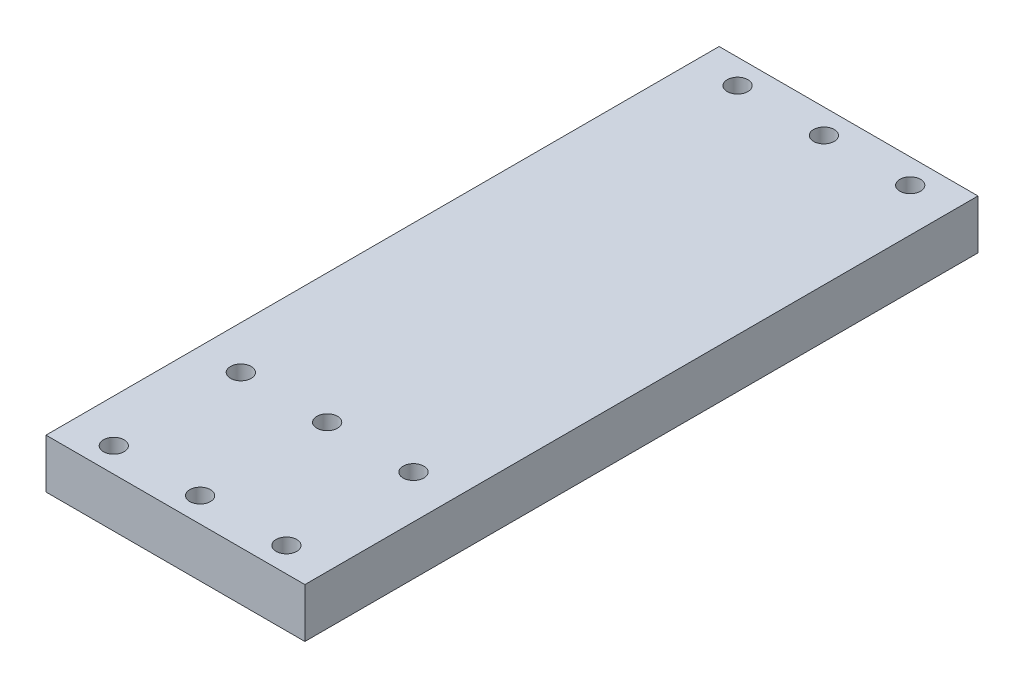
SolidWorks part; units mm, degrees
ref_plane "Front Plane" through (0, 0, 0) normal (0, 0, 1) x (1, 0, 0)
ref_plane "Top Plane" through (0, 0, 0) normal (0, 1, 0) x (1, 0, 0)
ref_plane "Right Plane" through (0, 0, 0) normal (1, 0, 0) x (0, 0, -1)
sketch "Sketch2" plane through (0, 0, 0) normal (0, 1, 0) x (1, 0, 0)
  line L1 (-25, -65) -> (25, -65)
  line L2 (-25, -65) -> (-25, 65)
  line L3 (-25, 65) -> (25, 65)
  line L4 (25, -65) -> (25, 65)
  line L5 (-25, -65) -> (25, 65) construction
  line L6 (-25, 65) -> (25, -65) construction
  point P0 (0, 0)
  dimension "D1" = 130
  dimension "D2" = 50
extrude "Boss-Extrude1" add sketch "Sketch2" along normal blind 9.525
sketch "Sketch3" plane through (0, 9.525, 0) normal (0, 1, 0) x (1, 0, 0)
  circle A0 centre (16.67, -60.2375) radius 2 construction
  circle A1 centre (0, -60.2375) radius 2 construction
  circle A2 centre (-16.67, -60.2375) radius 2 construction
  circle A3 centre (16.67, -35.7) radius 2 construction
  circle A4 centre (0, -35.7) radius 2 construction
  circle A5 centre (-16.67, -35.7) radius 2 construction
  circle A6 centre (16.67, 60.2375) radius 2 construction
  circle A7 centre (0, 60.2375) radius 2 construction
  circle A8 centre (-16.67, 60.2375) radius 2 construction
  circle A9 centre (16.67, -60.2375) radius 2
  circle A10 centre (0, -60.2375) radius 2
  circle A11 centre (-16.67, -60.2375) radius 2
  circle A12 centre (16.67, -35.7) radius 2
  circle A13 centre (0, -35.7) radius 2
  circle A14 centre (-16.67, -35.7) radius 2
  circle A15 centre (16.67, 60.2375) radius 2
  circle A16 centre (0, 60.2375) radius 2
  circle A17 centre (-16.67, 60.2375) radius 2
  point P29 (-16.67, 60.2375)
  point P32 (0, 60.2375)
  point P35 (16.67, 60.2375)
  point P38 (16.67, -35.7)
  point P41 (0, -35.7)
  point P44 (-16.67, -35.7)
  point P47 (-16.67, -60.2375)
  point P50 (0, -60.2375)
  point P53 (16.67, -60.2375)
hole_wizard "Ø4.0mm Dowel Hole1" positions "Sketch3" profile "Sketch5" hole size "Ø4.0" standard "ANSI Metric" end condition through all
sketch "Sketch5" plane through (16.67, 9.525, 60.2375) normal (1, 0, 0) x (0, 0, 1)
  line L0 (0, 0) -> (0, 9.525)
  line L1 (0, 9.525) -> (2, 9.525)
  line L2 (2, 9.525) -> (2, 0)
  line L5 (2, 0) -> (0, 0)
  line L11 (0, -6.35) -> (0, 107.95) construction
  dimension "Thru Hole Dia." = 4
  dimension "Thru Hole Depth" = 9.525
